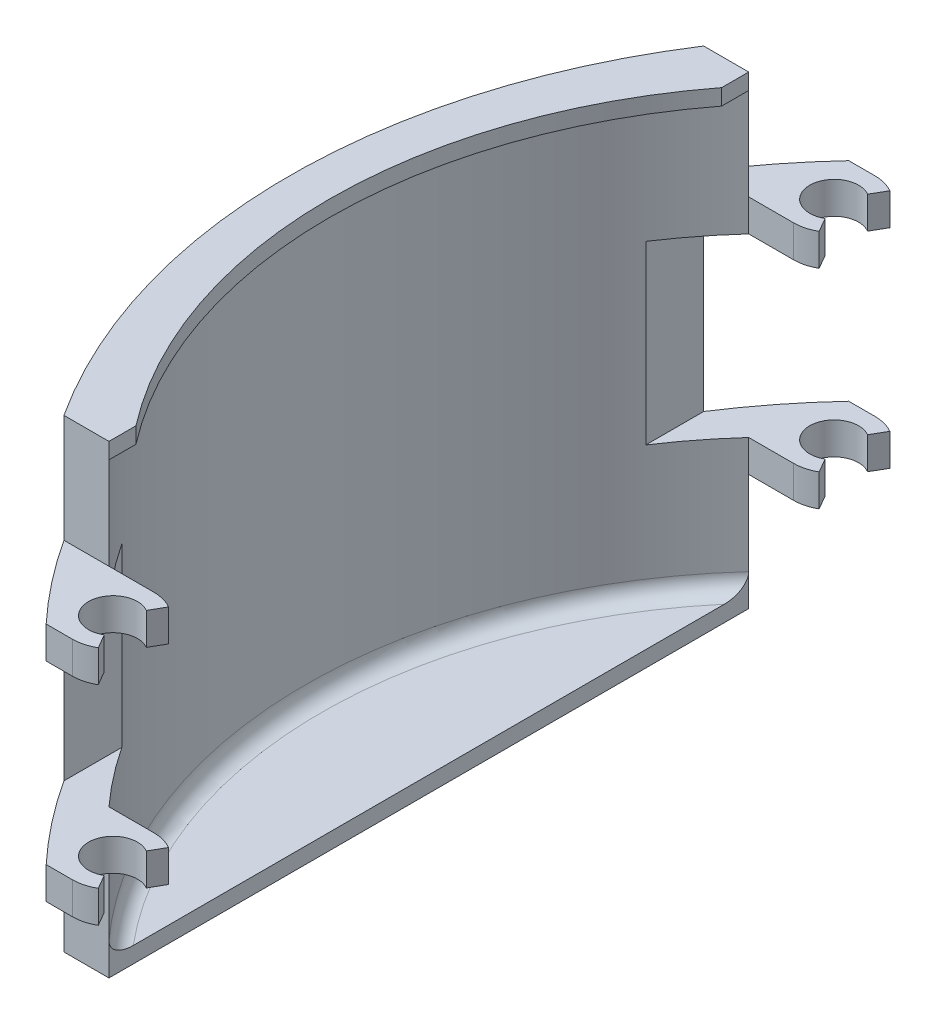
SolidWorks part; units mm, degrees
ref_plane "Front Plane" through (0, 0, 0) normal (0, 0, 1) x (1, 0, 0)
ref_plane "Top Plane" through (0, 0, 0) normal (0, 1, 0) x (1, 0, 0)
ref_plane "Right Plane" through (0, 0, 0) normal (1, 0, 0) x (0, 0, -1)
sketch "Sketch2" plane through (0, 0, 0) normal (0, 1, 0) x (1, 0, 0)
  line L2 (3.4168, 51.52) -> (43.1499, 51.52) construction
  line L3 (0.0958, 91.44) -> (5.6838, 91.44)
  line L8 (2.4212, 101.6) -> (5.6838, 101.6)
  line L11 (2.4212, 1.44) -> (5.6838, 1.44)
  line L12 (0.0958, 11.6) -> (5.6838, 11.6)
  line L13 (-17.3407, 51.52) -> (-15.3407, 51.52) construction
  arc A2 (5.6838, 91.44) -> (5.6838, 101.6) centre (5.6838, 96.52) ccw
  circle A3 centre (5.6838, 96.52) radius 3.048
  circle A6 centre (5.6838, 6.52) radius 3.048
  arc A7 (5.6838, 11.6) -> (5.6838, 1.44) centre (5.6838, 6.52) cw
  arc A10 (2.4212, 1.44) -> (2.4212, 101.6) centre (55.9958, 51.52) cw
  arc A11 (0.0958, 11.6) -> (0.0958, 91.44) centre (43.9958, 51.52) cw
  dimension "D2" = 2
  dimension "D7" = 2.032
  dimension "D8" = 6.096
  dimension "D1" = 45
extrude "Boss-Extrude1" add sketch "Sketch2" along normal blind 56
sketch "Sketch6" plane through (0, 56, 0) normal (0, 1, 0) x (1, 0, 0)
  line L0 (-15.3407, 51.52) -> (43.9958, 51.52) construction
  line L1 (5.6838, 6.52) -> (11.4571, 16.5935)
  line L2 (11.4571, 16.5935) -> (11.4571, -3.4065)
  line L3 (11.4571, -3.4065) -> (5.6838, 6.52)
  arc A0 (0.0958, 91.44) -> (0.0958, 11.6) centre (43.9958, 51.52) ccw construction
  dimension "D1" = 120
  dimension "D2" = 20
ref_plane "Plane1" through (0, 0, -51.52) normal (0, 0, 1) x (1, 0, 0)
extrude "Cut-Extrude2" cut sketch "Sketch6" against normal through all both and the other way through all contours L1 L2 L3
mirror "Mirror1" about plane through (0, 0, -51.52) normal (0, 0, 1) of "Cut-Extrude2"
ref_plane "Plane2" through (5.6838, 56, -1.44) normal (0, -1, 0) x (-1, 0, 0)
sketch "Sketch12" plane through (0, 0, -1.44) normal (0, 0, 1) x (1, 0, 0)
  line L0 (2.4212, 56) -> (2.4212, 0) construction
  line L1 (2.4212, 40.5) -> (8.2378, 40.5)
  line L2 (2.4212, 40.5) -> (2.4212, 18.5)
  line L3 (2.4212, 18.5) -> (8.2378, 18.5)
  line L4 (8.2378, 40.5) -> (8.2378, 18.5)
  line L5 (8.2378, 56) -> (8.2378, 0) construction
  line L6 (-49.3162, 56) -> (60.6838, 56) construction
  line L7 (2.4212, 56) -> (8.2378, 56)
  line L8 (2.4212, 56) -> (2.4212, 44.5)
  line L9 (2.4212, 44.5) -> (8.2378, 44.5)
  line L10 (8.2378, 56) -> (8.2378, 44.5)
  line L12 (2.4212, 0) -> (8.2378, 0)
  line L13 (2.4212, 0) -> (2.4212, 14.5)
  line L14 (2.4212, 14.5) -> (8.2378, 14.5)
  line L15 (8.2378, 0) -> (8.2378, 14.5)
  point P19 (5.3295, 44.5)
  dimension "D1" = 30
  dimension "D2" = 11.5
  dimension "D3" = 22
  dimension "D4" = 4
extrude "Cut-Extrude3" cut sketch "Sketch12" against normal through all both and the other way through all
sketch "Sketch13" plane through (2.4212, 0, 0) normal (1, 0, 0) x (0, 0, -1)
  line L0 (101.6, 56) -> (101.6, 44.5) construction
  line L1 (11.6, 44.5) -> (1.44, 44.5)
  line L2 (11.6, 44.5) -> (11.6, 56)
  line L3 (11.6, 56) -> (1.44, 56)
  line L4 (1.44, 44.5) -> (1.44, 56)
  line L5 (1.44, 14.5) -> (11.6, 14.5)
  line L6 (1.44, 14.5) -> (1.44, 0)
  line L7 (1.44, 0) -> (11.6, 0)
  line L8 (11.6, 14.5) -> (11.6, 0)
  line L9 (91.44, 56) -> (101.6, 56)
  line L10 (91.44, 56) -> (91.44, 44.5)
  line L11 (91.44, 44.5) -> (101.6, 44.5)
  line L12 (101.6, 56) -> (101.6, 44.5)
  line L14 (101.6, 0) -> (91.44, 0)
  line L15 (101.6, 0) -> (101.6, 14.5)
  line L16 (101.6, 14.5) -> (91.44, 14.5)
  line L17 (91.44, 0) -> (91.44, 14.5)
  point P25 (101.6, 41.5)
extrude "Cut-Extrude4" cut sketch "Sketch13" against normal blind 10
fillet "Fillet1" radius 10 2 edges at (2.4212, 29.5, -91.44) (2.4212, 29.5, -11.6)
sketch "Sketch15" plane through (0, 0, 0) normal (0, -1, 0) x (-1, 0, 0)
  line L0 (-0.0958, 11.6) -> (-0.0958, 91.44)
  arc A0 (-0.0958, 91.44) -> (-0.0958, 11.6) centre (-43.9958, 51.52) cw
extrude "Boss-Extrude2" add sketch "Sketch15" against normal blind 2
fillet "Fillet2" radius 2 1 edges at (-15.3407, 2, -51.52)
sketch "Sketch17" plane through (0, 56, 0) normal (0, 1, 0) x (1, 0, 0)
  line L0 (0.0958, 11.6) -> (5.6838, 11.6) construction
  line L1 (5.6838, 91.44) -> (0.0958, 91.44) construction
  line L2 (2.8898, 91.44) -> (-5.5236, 91.44)
  line L3 (2.8898, 11.6) -> (-5.5236, 11.6)
  line L4 (-17.3407, 51.52) -> (-12.3407, 51.52) construction
  arc A0 (2.8898, 11.6) -> (2.8898, 91.44) centre (47.5909, 51.52) cw
  arc A2 (-5.5236, 11.6) -> (-5.5236, 91.44) centre (55.9958, 51.52) cw
  dimension "D1" = 5
extrude "Boss-Extrude3" add sketch "Sketch17" along normal blind 2
sketch "Sketch18" plane through (0, 58, 0) normal (0, 1, 0) x (1, 0, 0)
  line L1 (0.0958, 11.6) -> (2.9741, 11.6)
  line L2 (0.0958, 11.6) -> (0.0958, 15.1418)
  line L3 (0.0958, 15.1418) -> (2.9741, 15.1418)
  line L4 (2.9741, 11.6) -> (2.9741, 15.1418)
  line L5 (0.0958, 91.44) -> (3.2623, 91.44)
  line L6 (0.0958, 91.44) -> (0.0958, 87.8553)
  line L7 (0.0958, 87.8553) -> (3.2623, 87.8553)
  line L8 (3.2623, 91.44) -> (3.2623, 87.8553)
extrude "Cut-Extrude5" cut sketch "Sketch18" against normal blind 2
sketch "Sketch19" plane through (0, 0, -11.6) normal (0, 0, 1) x (1, 0, 0)
  line L0 (2.4212, 18.5) -> (-17.3407, 18.5) construction
  line L1 (2.4212, 40.5) -> (-5.5207, 40.5)
  line L2 (2.4212, 40.5) -> (2.4212, 18.5)
  line L3 (2.4212, 18.5) -> (-5.5207, 18.5)
  line L4 (-5.5207, 40.5) -> (-5.5207, 18.5)
  line L7 (-17.3407, 44.5) -> (-17.3407, 18.5) construction
  dimension "D1" = 11.82
extrude "Cut-Extrude7" cut sketch "Sketch19" against normal through all both and the other way through all
